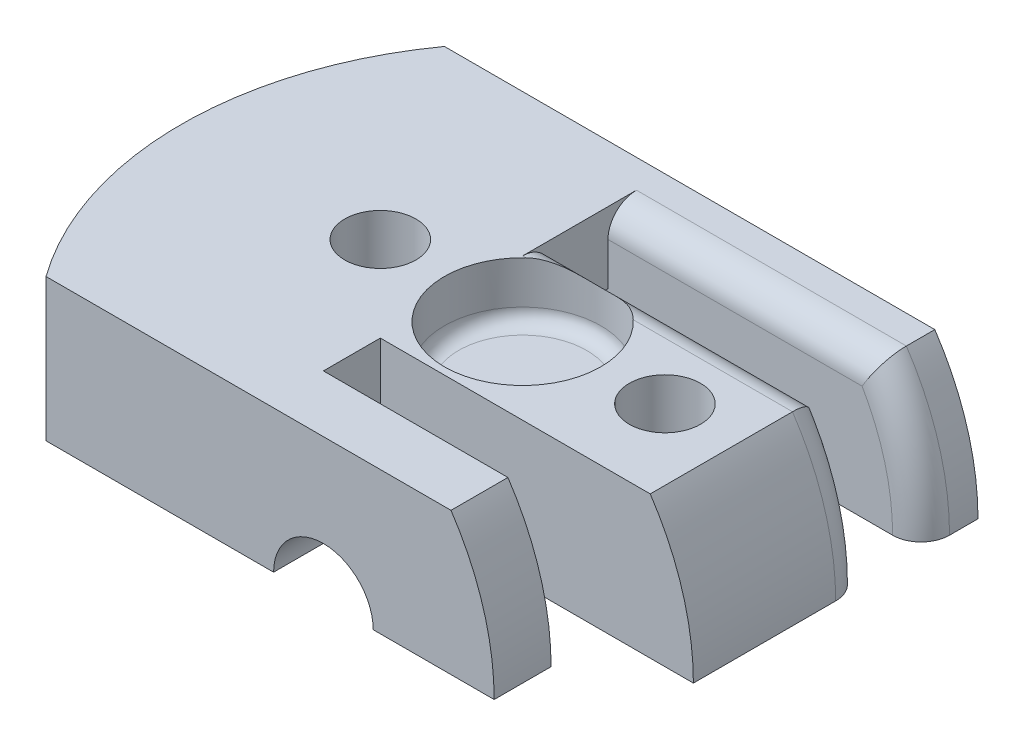
SolidWorks part; units mm, degrees
ref_plane "Front" through (0, 0, 0) normal (0, 0, 1) x (1, 0, 0)
ref_plane "Top" through (0, 0, 0) normal (0, 1, 0) x (1, 0, 0)
ref_plane "Right" through (0, 0, 0) normal (1, 0, 0) x (0, 0, -1)
sketch "Sketch1" plane through (0, 0, 0) normal (0, 1, 0) x (1, 0, 0)
  line L0 (21, 15) -> (21, 8)
  line L1 (12, 8) -> (12, 15) construction
  line L2 (12, 8) -> (12, 1) construction
  line L4 (12, 8) -> (21, 8) construction
  line L7 (21, 15) -> (12, 15)
  line L8 (12, 15) -> (2.2532, 15)
  line L10 (2.2532, 1) -> (12, 1)
  line L12 (12, 1) -> (21, 1)
  line L14 (21, 1) -> (21, 8)
  arc A1 (2.2532, 15) -> (2.2532, 1) centre (12, 8) ccw
extrude "Boss-Extrude1" add sketch "Sketch1" along normal blind 10
sketch "Sketch4" plane through (0, 0, 0) normal (0, 0, 1) x (1, 0, 0)
  line L0 (21, 5) -> (12, 5) construction
  line L2 (12, 14) -> (21, 14)
  line L3 (21, 14) -> (21, -4)
  line L4 (21, -4) -> (12, -4)
  arc A0 (12, 14) -> (12, -4) centre (12, 5) cw
extrude "Cut-Extrude3" cut sketch "Sketch4" against normal through all contours L2 A0 L3 | L3 A0 L4 region at (18.9897, -1.9897, 0) region at (18.9897, 11.9897, 0)
sketch "Sketch7" plane through (0, 0, 0) normal (0, 0, 1) x (1, 0, 0)
  line L0 (21, 5.5) -> (21, 11)
  line L1 (21, 5.5) -> (12, 5.5) construction
  line L2 (21, 11) -> (10, 11)
  line L4 (10, 11) -> (10, 7.5)
  line L5 (10, 7.5) -> (0, 7.5)
  line L7 (0, 7.5) -> (0, 3.5)
  line L8 (0, 3.5) -> (21, 3.5)
  line L9 (21, 3.5) -> (21, 5.5)
extrude "Cut-Extrude6" cut sketch "Sketch7" along normal blind 2 from offset 13 offset against normal yes
sketch "Sketch21" plane through (0, 0, 0) normal (0, 0, 1) x (1, 0, 0)
  line L0 (21, 5.5) -> (21, 11)
  line L1 (21, 5.5) -> (12, 5.5) construction
  line L2 (21, 11) -> (10, 11)
  line L4 (10, 11) -> (10, 7.5)
  line L5 (10, 7.5) -> (0, 7.5)
  line L7 (0, 7.5) -> (0, 3.5)
  line L8 (0, 3.5) -> (21, 3.5)
  line L9 (21, 3.5) -> (21, 5.5)
extrude "Cut-Extrude14" cut sketch "Sketch21" against normal blind 2 from offset 3 offset against normal yes
sketch "Sketch8" plane through (0, 0, 0) normal (0, 1, 0) x (1, 0, 0)
  circle A1 centre (12, 8) radius 2.75
extrude "Cut-Extrude7" cut sketch "Sketch8" against normal blind 2 from offset 10
sketch "Sketch10" plane through (0, 0, 0) normal (0, 0, 1) x (1, 0, 0)
  circle A0 centre (12, 5) radius 2.25
extrude "Cut-Extrude8" cut sketch "Sketch10" along normal blind 3 from offset 16 offset against normal yes
sketch "Sketch11" plane through (0, 0, 0) normal (1, 0, 0) x (0, 0, -1)
  line L0 (8, 0) -> (8, 2) construction
  line L2 (8, 2) -> (13, 2)
  line L3 (13, 2) -> (13, 8)
  line L4 (13, 8) -> (3, 8)
  line L5 (3, 8) -> (3, 2)
  line L6 (3, 2) -> (8, 2)
extrude "Cut-Extrude9" cut sketch "Sketch11" along normal blind 5
sketch "Sketch18" plane through (0, 0, 0) normal (0, 0, 1) x (1, 0, 0)
  circle A0 centre (12, 5) radius 0.75
extrude "Cut-Extrude12" cut sketch "Sketch18" against normal through all
sketch "Sketch19" plane through (0, 0, 0) normal (0, 1, 0) x (1, 0, 0)
  line L0 (10, 10) -> (14, 10)
  line L3 (14, 10) -> (14, 6)
  line L4 (14, 6) -> (10, 6)
  line L5 (10, 6) -> (10, 10)
extrude "Cut-Extrude13" cut sketch "Sketch19" along normal mid plane 2 from offset 5
sketch "Sketch5" plane through (0, 0, 0) normal (0, 0, 1) x (1, 0, 0)
  circle A1 centre (12, 5) radius 1.75
extrude "Cut-Extrude15" cut sketch "Sketch5" against normal blind 2 from offset 1 offset against normal yes
sketch "Sketch26" plane through (0, 0, 0) normal (0, 0, 1) x (1, 0, 0)
  line L0 (16.4833, 10) -> (19.4833, 10)
  line L3 (20.8741, 3.5) -> (17.8741, 3.5)
  arc A1 (20.8741, 3.5) -> (19.4833, 10) centre (12, 5) ccw
  arc A2 (17.8741, 3.5) -> (16.4833, 10) centre (9, 5) ccw
extrude "Cut-Extrude16" cut sketch "Sketch26" against normal blind 2 from offset 1 offset against normal yes
fillet "Fillet2" radius 0.5 1 edges at (12, 8, -5.25)
fillet "Fillet3" radius 1 4 edges at (20.8008, 6.8831, -13) (14.7417, 10, -13) (20.8008, 6.8831, -11) (14.7417, 10, -11)
sketch "Sketch3" plane through (28.2876, 0, 0) normal (0, 1, 0) x (1, 0, 0)
  line L0 (-25.2876, 12.5) -> (-20.5376, 12.5)
  line L1 (-25.2876, 3.5) -> (-20.5376, 3.5)
  line L26 (-16.2876, 8) -> (-9.2876, 8) construction
  line L27 (-16.2876, 8) -> (-25.2876, 8) construction
  line L28 (-16.2876, 8) -> (-16.2876, 2.5) construction
  line L29 (-16.2876, 8) -> (-16.2876, 13.5) construction
  line L30 (-9.2876, 8) -> (-9.2876, 9.5001)
  line L31 (-9.2876, 9.5001) -> (-10.7911, 9.5001)
  line L32 (-10.7911, 9.5001) -> (-12.2911, 9.5001) construction
  line L33 (-12.2911, 9.5001) -> (-12.2911, 12.5001) construction
  line L34 (-10.7911, 9.5001) -> (-12.2911, 12.5001)
  line L35 (-12.2911, 12.5001) -> (-12.2911, 13.5)
  line L36 (-12.2911, 13.5) -> (-16.2876, 13.5)
  line L37 (-16.2876, 13.5) -> (-20.5376, 13.5)
  line L38 (-20.5376, 13.5) -> (-20.5376, 12.5)
  line L40 (-25.2876, 12.5) -> (-25.2876, 8)
  line L41 (-9.2876, 8) -> (-9.2876, 6.5)
  line L42 (-9.2876, 6.5) -> (-10.7876, 6.5)
  line L43 (-10.7876, 6.5) -> (-12.2876, 6.5) construction
  line L44 (-12.2876, 6.5) -> (-12.2876, 3.5) construction
  line L45 (-10.7876, 6.5) -> (-12.2876, 3.5)
  line L46 (-12.2876, 3.5) -> (-12.2876, 2.5)
  line L47 (-12.2876, 2.5) -> (-16.2876, 2.5)
  line L48 (-16.2876, 2.5) -> (-20.5376, 2.5)
  line L49 (-20.5376, 2.5) -> (-20.5376, 3.5)
  line L51 (-25.2876, 3.5) -> (-25.2876, 8)
extrude "Pot Insert" cut sketch "Sketch3" along normal blind 2.5
sketch "Sketch6" plane through (0, 0, 0) normal (0, 1, 0) x (1, 0, 0)
  circle A1 centre (12, 8) radius 2.75
extrude "Pot Hole" cut sketch "Sketch6" along normal blind 1.5 from offset 2.5
sketch "Sketch14" plane through (0, 0, 0) normal (0, 1, 0) x (1, 0, 0)
  line L0 (12, 8) -> (17, 8) construction
  line L1 (12, 8) -> (7, 8) construction
  circle A0 centre (7, 8) radius 0.8
  circle A1 centre (17, 8) radius 0.8
extrude "Screw Holes" cut sketch "Sketch14" against normal blind 9 from offset 11
sketch "Sketch15" plane through (0, 0, 0) normal (0, 1, 0) x (1, 0, 0)
  circle A0 centre (7, 8) radius 1.25
  circle A1 centre (17, 8) radius 1.25
extrude "Screw Heads" cut sketch "Sketch15" against normal blind 2 from offset 10
sketch "Sketch13" plane through (0, 0, 0) normal (0, 1, 0) x (1, 0, 0)
  line L1 (21, 15) -> (0, 15)
  line L2 (21, 15) -> (21, 0)
  line L3 (21, 0) -> (0, 0)
  line L4 (0, 15) -> (0, 0)
extrude "Cut-Extrude11" cut sketch "Sketch13" along normal blind 5
